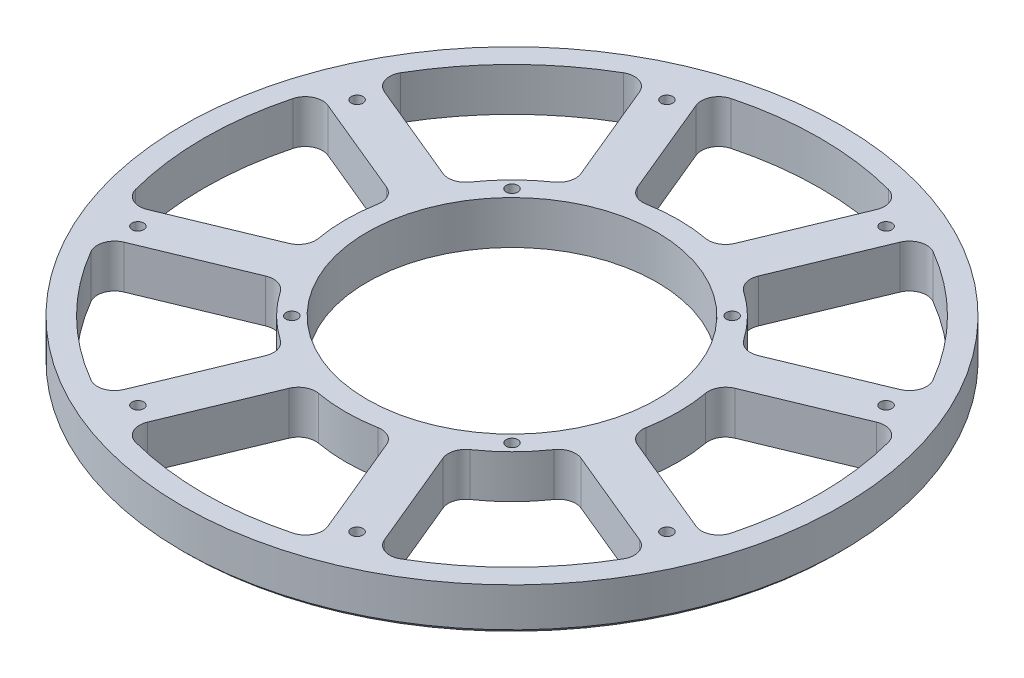
SolidWorks part; units mm, degrees
ref_plane "Front Plane" through (0, 0, 0) normal (0, 0, 1) x (1, 0, 0)
ref_plane "Top Plane" through (0, 0, 0) normal (0, 1, 0) x (1, 0, 0)
ref_plane "Right Plane" through (0, 0, 0) normal (1, 0, 0) x (0, 0, -1)
sketch "Sketch2" plane through (0, 0, 0) normal (1, 0, 0) x (0, 0, -1)
  line L0 (0, 0) -> (-76.2, 0)
  line L1 (-76.2, 0) -> (-76.2, 10)
  line L2 (-76.2, 10) -> (0, 10)
  line L5 (0, 10) -> (0, 0)
  dimension "D1" = 76.2
  dimension "D2" = 10
ref_axis "Axis1" through (0, -0.5, 0) along (0, 1, 0)
revolve "Revolve1" add sketch "Sketch2" angle 360 about axis through (0, -0.5, 0) along (0, 1, 0)
hole_wizard "#6-32 Tapped Hole1" positions "Sketch6" profile "Sketch7" tap size "#6-32" standard "ANSI Inch" end condition through all
sketch "Sketch6" plane through (0, 10, 0) normal (0, 1, 0) x (1, 0, 0)
  line L0 (0, 0) -> (-53.438, 129.0108) construction
  line L2 (0, 0) -> (0, 109.0908) construction
  line L3 (0, 0) -> (-70.3996, 29.1605) construction
  line L4 (0, 0) -> (-68.4315, 68.4315) construction
  circle A0 centre (0, 0) radius 76.2 construction
  point P0 (-25.3336, 61.1608)
  point P18 (-61.1608, 25.3336)
  point P27 (-25.4558, 25.4558)
  dimension "D1" = 22.5
  dimension "D2" = 66.2
  dimension "D3" = 45
  dimension "D4" = 66.2
  dimension "D6" = 22.5
  dimension "D5" = 36
sketch "Sketch7" plane through (-25.3336, 10, -61.1608) normal (1, 0, 0) x (0, 0, 1)
  line L0 (0, 0) -> (0, 10)
  line L1 (0, 10) -> (1.3525, 10)
  line L2 (1.3525, 10) -> (1.3525, 0)
  line L5 (1.3525, 0) -> (0, 0)
  line L11 (0, -6.35) -> (0, 107.95) construction
  dimension "Thread Major Dia." = 2.7051
  dimension "Thru Tap Drill Depth" = 10
pattern_circular "CirPattern3" count 4 over 360 about axis through (0, -0.5, 0) along (0, 1, 0) of "#6-32 Tapped Hole1"
sketch "Sketch8" plane through (0, 10, 0) normal (0, 1, 0) x (1, 0, 0)
  line L4 (0, 0) -> (0, 93.9995) construction
  line L5 (0, 0) -> (113.8372, 0) construction
  line L6 (-9.9891, 37.1815) -> (-22.5604, 67.5312)
  line L7 (9.9891, 37.1815) -> (22.5604, 67.5312)
  line L8 (0, 0) -> (-25.3336, 61.1608) construction
  arc A0 (-9.9891, 37.1815) -> (9.9891, 37.1815) centre (0, 0) cw
  arc A1 (-22.5604, 67.5312) -> (22.5604, 67.5312) centre (0, 0) cw
  circle A2 centre (0, 0) radius 76.2 construction
  dimension "D1" = 38.5
  dimension "D2" = 5
  dimension "D3" = 5
extrude "Cut-Extrude1" cut sketch "Sketch8" against normal through all
fillet "Fillet1" radius 4 4 edges at (9.9891, 5, -37.1815) (22.5604, 5, -67.5312) (-9.9891, 5, -37.1815) (-22.5604, 5, -67.5312)
pattern_circular "CirPattern4" count 8 over 360 about axis through (0, -0.5, 0) along (0, 1, 0) of "Cut-Extrude1", "Fillet1"
chamfer "Chamfer2" distance 1 angle 45 1 edges at (0, 0, -76.2)
sketch "Sketch9" plane through (0, 10, 0) normal (0, 1, 0) x (1, 0, 0)
  circle A0 centre (0, 0) radius 33.5
  dimension "D1" = 67
extrude "Cut-Extrude2" cut sketch "Sketch9" against normal through all
equation "\"TubeDiameter\" = 6.000in"
equation "\"D1@Sketch2\"=\"TubeDiameter\"/2"
equation "\"D2@Sketch6\"=\"TubeDiameter\"/2-10mm"
